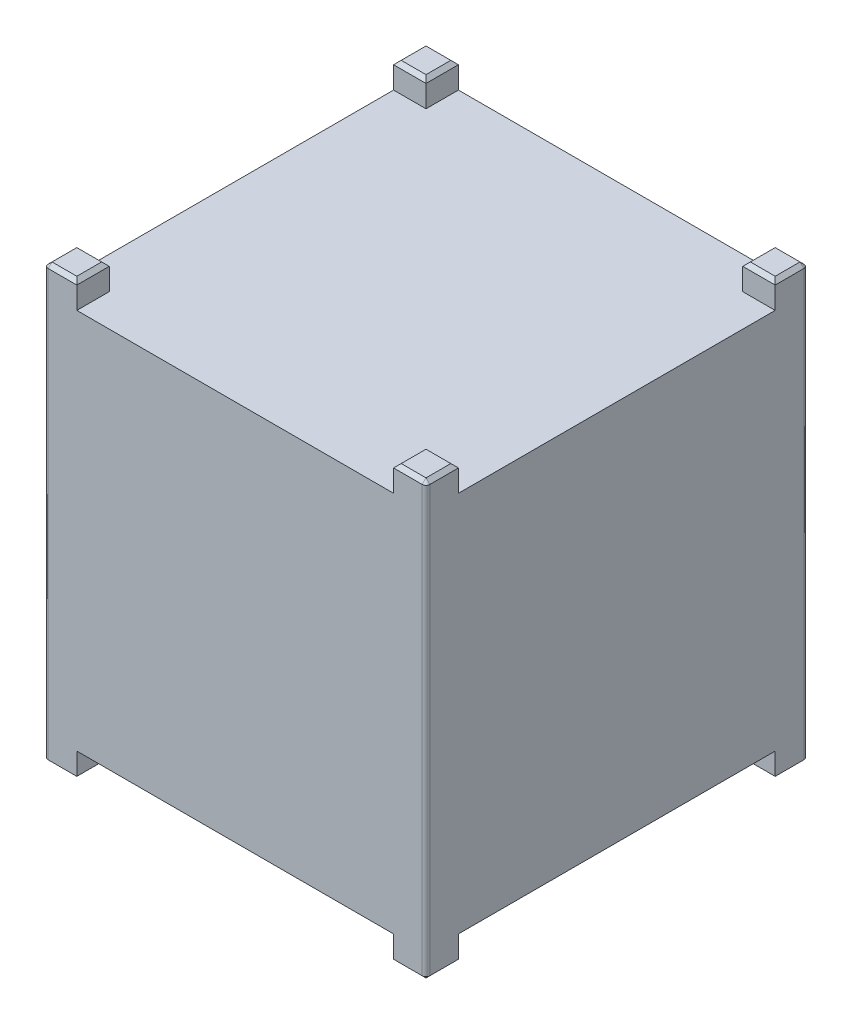
SolidWorks part; units mm, degrees
ref_plane "Front" through (0, 0, 0) normal (0, 0, 1) x (1, 0, 0)
ref_plane "Top" through (0, 0, 0) normal (0, 1, 0) x (1, 0, 0)
ref_plane "Right" through (0, 0, 0) normal (1, 0, 0) x (0, 0, -1)
ref_axis "Z AXIS" through (0, -55, 0) along (0, 1, 0)
ref_axis "Y AXIS" through (88.99, 0, 0) along (-1, 0, 0)
ref_axis "X AXIS" through (0, 0, -80.9) along (0, 0, 1)
sketch "CG SKETCH" plane through (0, 0, 0) normal (0, 1, 0) x (1, 0, 0)
  line L0 (0, 80.9) -> (0, -80.9) construction
  line L1 (0, -20) -> (0, 20)
  line L2 (88.99, 0) -> (-88.99, 0) construction
  arc A0 (0, -20) -> (0, 20) centre (0, 0) cw
  dimension "D1" = 20
revolve "CENTER OF GRAVITY" add sketch "CG SKETCH" angle 360 about axis through (0, 0, -80.9) along (0, 0, 1)
sketch "PERIMETER SKETCH" plane through (0, 0, 0) normal (0, 1, 0) x (1, 0, 0)
  line L1 (-50, 50) -> (50, 50)
  line L2 (-50, 50) -> (-50, -50)
  line L3 (-50, -50) -> (50, -50)
  line L4 (50, 50) -> (50, -50)
  line L5 (-50, 50) -> (50, -50) construction
  line L6 (-50, -50) -> (50, 50) construction
  point P0 (0, 0)
  dimension "D1" = 100
  dimension "D2" = 100
extrude "PERIMETER" add sketch "PERIMETER SKETCH" along normal blind 50 and the other way blind 50 separate body
sketch "RAIL SKETCH" plane through (0, 0, 0) normal (0, 1, 0) x (1, 0, 0)
  line L0 (-50, -50) -> (50, 50) construction
  line L1 (-50, 50) -> (-41.5, 50)
  line L2 (-50, 50) -> (-50, 41.5)
  line L3 (-50, 41.5) -> (-41.5, 41.5)
  line L4 (-41.5, 50) -> (-41.5, 41.5)
  line L5 (50, 50) -> (41.5, 50)
  line L6 (50, 50) -> (50, 41.5)
  line L7 (50, 41.5) -> (41.5, 41.5)
  line L8 (41.5, 50) -> (41.5, 41.5)
  line L10 (-50, -50) -> (-41.5, -50)
  line L11 (-50, -50) -> (-50, -41.5)
  line L12 (-50, -41.5) -> (-41.5, -41.5)
  line L13 (-41.5, -50) -> (-41.5, -41.5)
  line L14 (50, -50) -> (41.5, -50)
  line L15 (50, -50) -> (50, -41.5)
  line L16 (50, -41.5) -> (41.5, -41.5)
  line L17 (41.5, -50) -> (41.5, -41.5)
  dimension "D1" = 8.5
  dimension "D2" = 8.5
extrude "RAILS" add sketch "RAIL SKETCH" along normal blind 56.75 and the other way blind 56.75
fillet "Fillet1" radius 1 4 edges at (-50, 0, -50) (50, 0, -50) (50, 0, 50) (-50, 0, 50)
chamfer "Chamfer1" distance 1 angle 45 40 edges at (-45.25, -56.75, 50) (-41.5, -56.75, 45.75) (-45.75, -56.75, 41.5) (-50, -56.75, 45.25) (45.75, -56.75, 41.5) (41.5, -56.75, 45.75) (45.25, -56.75, 50) (50, -56.75, 45.25) (-45.75, -56.75, -41.5) (-41.5, -56.75, -45.75) (-45.25, -56.75, -50) (-50, -56.75, -45.25) (45.25, -56.75, -50) (41.5, -56.75, -45.75) (45.75, -56.75, -41.5) (50, -56.75, -45.25) (45.25, 56.75, 50) (41.5, 56.75, 45.75) (45.75, 56.75, 41.5) (50, 56.75, 45.25) (-45.75, 56.75, 41.5) (-41.5, 56.75, 45.75) (-45.25, 56.75, 50) (-50, 56.75, 45.25) (45.75, 56.75, -41.5) (41.5, 56.75, -45.75) (45.25, 56.75, -50) (50, 56.75, -45.25) (-45.25, 56.75, -50) (-41.5, 56.75, -45.75) (-45.75, 56.75, -41.5) (-50, 56.75, -45.25) (-49.7071, -56.75, 49.7071) (49.7071, -56.75, 49.7071) (-49.7071, -56.75, -49.7071) (49.7071, -56.75, -49.7071) (49.7071, 56.75, 49.7071) (-49.7071, 56.75, 49.7071) (49.7071, 56.75, -49.7071) (-49.7071, 56.75, -49.7071)
ref_plane "OUTER Z+ FACE" through (0, 50, 0) normal (0, 1, 0) x (1, 0, 0)
ref_plane "OUTER Z- FACE" through (0, -50, 0) normal (0, 1, 0) x (1, 0, 0)
ref_plane "TOP OF STAMPING EDGE" through (0, 48, 0) normal (0, 1, 0) x (1, 0, 0)
ref_plane "BOTTOM OF STAMPING EDGE" through (0, -48, 0) normal (0, 1, 0) x (1, 0, 0)
ref_plane "FLOOR 2" through (0, -36, 0) normal (0, 1, 0) x (1, 0, 0)
ref_plane "FLOOR 3" through (0, -24, 0) normal (0, 1, 0) x (1, 0, 0)
ref_plane "FLOOR 4" through (0, -12, 0) normal (0, 1, 0) x (1, 0, 0)
ref_plane "FLOOR 5" through (0, 0, 0) normal (0, 1, 0) x (1, 0, 0)
ref_plane "FLOOR 6" through (0, 12, 0) normal (0, 1, 0) x (1, 0, 0)
ref_plane "FLOOR 7" through (0, 24, 0) normal (0, 1, 0) x (1, 0, 0)
ref_plane "FLOOR 8" through (0, 36, 0) normal (0, 1, 0) x (1, 0, 0)
ref_plane "OUTER X- FACE" through (0, 0, 50) normal (0, 0, 1) x (1, 0, 0)
ref_plane "OUTER X+ FACE" through (0, 0, -50) normal (0, 0, 1) x (1, 0, 0)
ref_plane "OUTER Y- FACE" through (50, 0, 0) normal (1, 0, 0) x (0, 0, -1)
ref_plane "OUTER Y+ FACE" through (-50, 0, 0) normal (1, 0, 0) x (0, 0, -1)
ref_plane "RAIL KEEPOUT X-" through (0, 0, 41.5) normal (0, 0, 1) x (1, 0, 0)
ref_plane "RAIL KEEPOUT X+" through (0, 0, -41.5) normal (0, 0, 1) x (1, 0, 0)
ref_plane "RAIL KEEPOUT Y-" through (41.5, 0, 0) normal (1, 0, 0) x (0, 0, -1)
ref_plane "RAIL KEEPOUT Y+" through (-41.5, 0, 0) normal (1, 0, 0) x (0, 0, -1)
ref_plane "U SPLIT PLANE" through (0, 0, 33) normal (0, 0, 1) x (1, 0, 0)
sketch "U JOINT CENTER POINTS" plane through (0, 0, 0) normal (1, 0, 0) x (0, 0, -1)
  line L0 (55, 48) -> (-55, 48) construction
  line L1 (-33, 55) -> (-33, -55) construction
  line L2 (-36, 38) -> (-28, 38) construction
  line L3 (-36, -38) -> (-28, -38) construction
  line L4 (-36, -38) -> (-36, 38) construction
  line L5 (-28, 38) -> (-28, -38) construction
  line L6 (55, -48) -> (-55, -48) construction
  point P0 (-36, 38)
  point P2 (-28, -38)
  point P6 (-28, 38)
  point P7 (-36, -38)
  dimension "D1" = 10
  dimension "D2" = 3
  dimension "D3" = 8
  dimension "D4" = 10
ref_axis "UPPER SMALL U JOINT AXIS" through (0, 38, 36) along (1, 0, 0)
ref_axis "UPPER LARGE U JOINT AXIS" through (0, 38, 28) along (1, 0, 0)
ref_axis "LOWER SMALL U JOINT AXIS" through (0, -38, 36) along (1, 0, 0)
ref_axis "LOWER LARGE U JOINT AXIS" through (0, -38, 28) along (1, 0, 0)
ref_plane "BRACKET BOLTS X- PLANE" through (0, 0, 28) normal (0, 0, 1) x (1, 0, 0)
ref_plane "BRACKET BOLTS X+ PLANE" through (0, 0, -34.5) normal (0, 0, 1) x (1, 0, 0)
